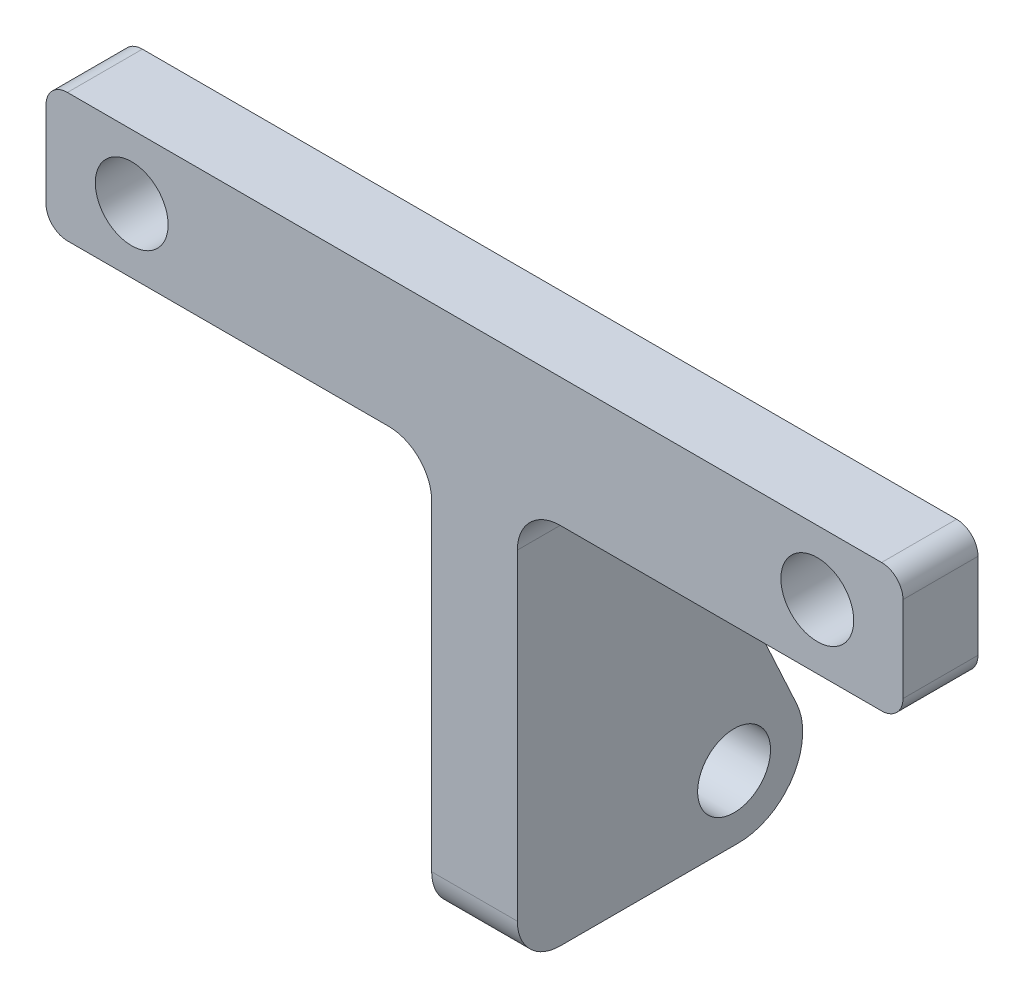
SolidWorks part; units mm, degrees
ref_plane "Front Plane" through (0, 0, 0) normal (0, 0, 1) x (1, 0, 0)
ref_plane "Top Plane" through (0, 0, 0) normal (0, 1, 0) x (1, 0, 0)
ref_plane "Right Plane" through (0, 0, 0) normal (1, 0, 0) x (0, 0, -1)
sketch "Sketch3" plane through (0, 0, 0) normal (0, 0, 1) x (1, 0, 0)
  line L0 (0, 0) -> (0, -3) construction
  line L1 (-19, -3) -> (19, -3)
  line L2 (-20, -2) -> (-20, 2)
  line L3 (-19, 3) -> (19, 3)
  line L4 (20, -2) -> (20, 2)
  line L5 (-20, -3) -> (20, 3) construction
  line L6 (-20, 3) -> (20, -3) construction
  arc A0 (-19, -3) -> (-20, -2) centre (-19, -2) cw
  arc A1 (-20, 2) -> (-19, 3) centre (-19, 2) cw
  arc A2 (19, -3) -> (20, -2) centre (19, -2) ccw
  arc A3 (19, 3) -> (20, 2) centre (19, 2) cw
  circle A4 centre (-16, 0) radius 1.7
  circle A5 centre (16, 0) radius 1.7
  point P0 (0, 0)
  dimension "D2" = 1
  dimension "D3" = 16
  dimension "D4" = 3.4
  dimension "D1" = 6
  dimension "D5" = 40
extrude "Boss-Extrude1" add sketch "Sketch3" along normal blind 3.5
sketch3d "3DSketch1"
  line L1 (0, 0, 0) -> (0, 3, 0) construction
  line L2 (19, 3, 0) -> (-19, 3, 0) construction
sketch3d "3DSketch2" plane through (0, 0, 0) normal (0, 0, 1) x (1, 0, 0)
  dimension "D1" = 90
sketch "Sketch4" plane through (0, 0, 0) normal (1, 0, 0) x (0, 0, -1)
  line L0 (0, 3) -> (11.5, -22)
  line L1 (11.5, -22) -> (-3.5, -22)
  line L2 (-3.5, -22) -> (-3.5, 3)
  line L3 (-3.5, 3) -> (0, 3)
  dimension "D1" = 3.5
  dimension "D2" = 15
  dimension "D3" = 25
extrude "Boss-Extrude2" add sketch "Sketch4" along normal mid plane 4
fillet "Fillet1" radius 2 5 edges at (2, -3, 1.75) (2, 0, 0) (-2, -3, 1.75) (-2, 0, 0) (0, -22, 3.5)
sketch "Sketch5" plane through (2, 0, 0) normal (1, 0, 0) x (0, 0, -1)
  circle A0 centre (6.6158, -18.9731) radius 1.7
  dimension "D1" = 3.4
extrude "Cut-Extrude1" cut sketch "Sketch5" against normal blind 4
fillet "Fillet2" radius 3 1 edges at (0, -22, -11.5)
